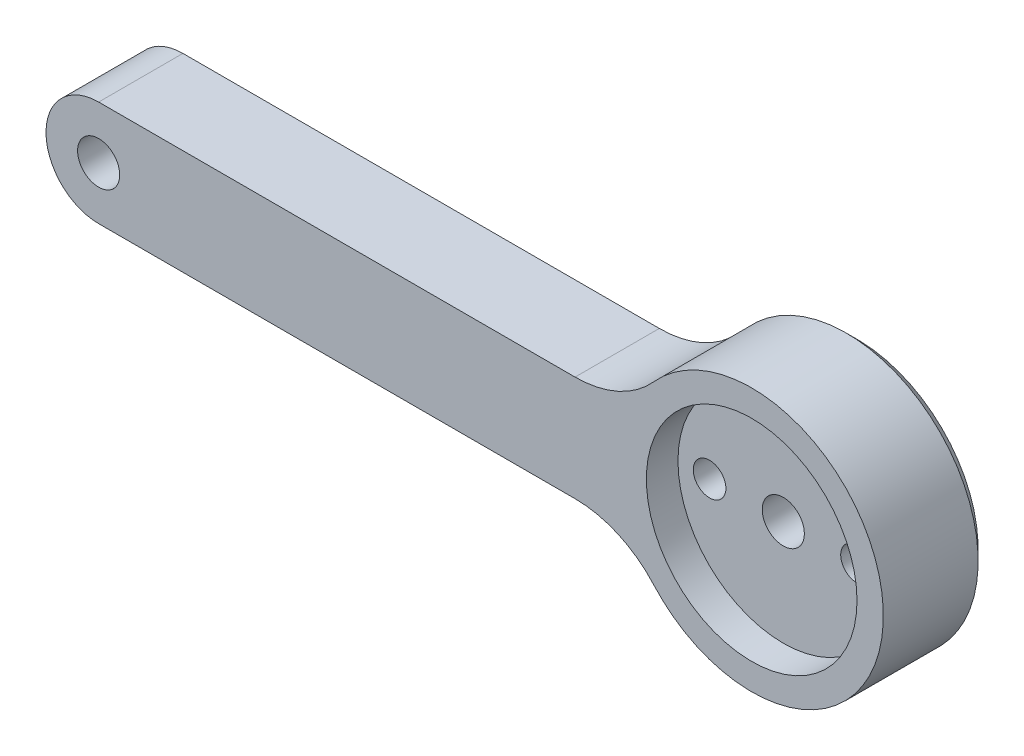
SolidWorks part; units mm, degrees
ref_plane "前视基准面" through (0, 0, 0) normal (0, 0, 1) x (1, 0, 0)
ref_plane "上视基准面" through (0, 0, 0) normal (0, 1, 0) x (1, 0, 0)
ref_plane "右视基准面" through (0, 0, 0) normal (1, 0, 0) x (0, 0, -1)
sketch "草图2" plane through (0, 0, 0) normal (0, 0, 1) x (1, 0, 0)
  line L0 (0, 0) -> (2, 0)
  line L1 (0, 5) -> (62, 5)
  line L2 (0, -5) -> (62, -5)
  line L3 (60, 0) -> (62, 0)
  circle A0 centre (0, 0) radius 2
  circle A1 centre (62, 0) radius 2
  arc A2 (0, 5) -> (0, -5) centre (0, 0) ccw
  arc A3 (62, -5) -> (62, 5) centre (62, 0) ccw
  dimension "D2" = 4
  dimension "D3" = 4
  dimension "D4" = 10
  dimension "D1" = 62
extrude "凸台-拉伸1" add sketch "草图2" along normal blind 8 contours L2 A3 L1 A2 A0 A1 region at (31, 0, 0)
sketch "草图3" plane through (0, 0, 8) normal (0, 0, 1) x (1, 0, 0)
  circle A0 centre (62, 0) radius 12.5
  circle A1 centre (62, 0) radius 10
  dimension "D1" = 25
  dimension "D2" = 20
extrude "凸台-拉伸2" add sketch "草图3" against normal blind 8
sketch "草图4" plane through (0, 0, 0) normal (0, 0, -1) x (-1, 0, 0)
  circle A0 centre (-62, 0) radius 10
  circle A1 centre (-62, 0) radius 2.0133
extrude "凸台-拉伸3" add sketch "草图4" against normal blind 5
sketch "草图5" plane through (0, 0, 8) normal (0, 0, 1) x (1, 0, 0)
  circle A0 centre (62, 0) radius 10
extrude "切除-拉伸1" cut sketch "草图5" against normal blind 3
fillet "圆角1" radius 10 2 edges at (50.5436, -5, 4) (50.5436, 5, 4)
sketch "草图6" plane through (0, 0, 5) normal (0, 0, 1) x (1, 0, 0)
  line L0 (52, 0) -> (72, 0) construction
  circle A0 centre (62, 0) radius 10 construction
  circle A1 centre (62, 0) radius 10 construction
  circle A2 centre (55, 0) radius 1.55
  circle A3 centre (69, 0) radius 1.55
  point P11 (62, 0)
  dimension "D1" = 3.1
  dimension "D2" = 3.1
  dimension "D4" = 7
  dimension "D3" = 7
extrude "切除-拉伸2" cut sketch "草图6" against normal through all
sketch "草图7" plane through (0, 0, 0) normal (0, 0, -1) x (-1, 0, 0)
  circle A0 centre (-62, 0) radius 12.5
  circle A1 centre (-62, 0) radius 10.5
  arc A2 (-52.6831, 8.3333) -> (-52.6831, -8.3333) centre (-62, 0) ccw construction
  dimension "D1" = 2
extrude "凸台-拉伸4" add sketch "草图7" along normal blind 2
chamfer "倒角1" distance 1 angle 45 2 edges at (51.5, 0, -2) (49.5, 0, -2)
sketch "草图8" plane through (0, 0, 0) normal (0, 0, -1) x (-1, 0, 0)
  line L0 (-43.1457, 0) -> (0, 0) construction
  line L1 (-40.4043, 0) -> (-38.4338, 2.9556)
  line L2 (-38.4338, 2.9556) -> (-34.9213, 2.9556)
  line L3 (-34.9213, 2.9556) -> (-36.8918, 0)
  line L4 (-30.4043, 0) -> (-28.4338, 2.9556)
  line L5 (-28.4338, 2.9556) -> (-24.9213, 2.9556)
  line L6 (-24.9213, 2.9556) -> (-26.8918, 0)
  line L7 (-20.4043, 0) -> (-18.4338, 2.9556)
  line L8 (-18.4338, 2.9556) -> (-14.9213, 2.9556)
  line L9 (-14.9213, 2.9556) -> (-16.8918, 0)
  line L10 (-10.4043, 0) -> (-8.4338, 2.9556)
  line L11 (-8.4338, 2.9556) -> (-4.9213, 2.9556)
  line L12 (-4.9213, 2.9556) -> (-6.8918, 0)
  line L13 (-4.9213, -2.9556) -> (-6.8918, 0)
  line L14 (-8.4338, -2.9556) -> (-4.9213, -2.9556)
  line L15 (-10.4043, 0) -> (-8.4338, -2.9556)
  line L16 (-14.9213, -2.9556) -> (-16.8918, 0)
  line L17 (-18.4338, -2.9556) -> (-14.9213, -2.9556)
  line L18 (-20.4043, 0) -> (-18.4338, -2.9556)
  line L19 (-24.9213, -2.9556) -> (-26.8918, 0)
  line L20 (-28.4338, -2.9556) -> (-24.9213, -2.9556)
  line L21 (-30.4043, 0) -> (-28.4338, -2.9556)
  line L22 (-34.9213, -2.9556) -> (-36.8918, 0)
  line L23 (-38.4338, -2.9556) -> (-34.9213, -2.9556)
  line L24 (-40.4043, 0) -> (-38.4338, -2.9556)
  dimension "D1" = 4
extrude "切除-拉伸3" cut sketch "草图8" against normal blind 1
